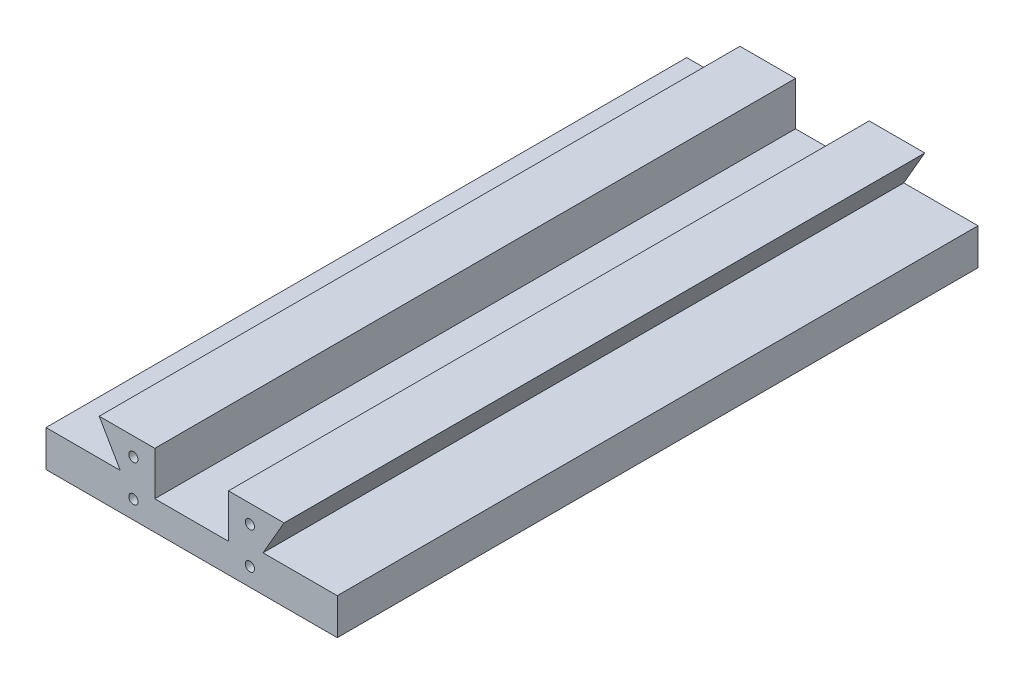
SolidWorks part; units mm, degrees
material "Ductile Iron"
ref_plane "Front Plane" through (0, 0, 0) normal (0, 0, 1) x (1, 0, 0)
ref_plane "Top Plane" through (0, 0, 0) normal (0, 1, 0) x (1, 0, 0)
ref_plane "Right Plane" through (0, 0, 0) normal (1, 0, 0) x (0, 0, -1)
sketch "dovetail-male-profile" plane through (0, 0, 0) normal (0, 0, 1) x (1, 0, 0)
  line L0 (47.4471, 31.496) -> (16.3103, 31.496)
  line L1 (-16.3103, 31.496) -> (-39.6952, 31.496)
  line L2 (16.3103, 31.496) -> (16.3103, 12.446)
  line L3 (16.3103, 12.446) -> (-16.3103, 12.446)
  line L4 (-16.3103, 12.446) -> (-16.3103, 31.496)
  line B0 (-63.5, 0) -> (63.5, 0)
  line B1 (63.5, 0) -> (63.5, 15.875)
  line B2 (63.5, 15.875) -> (38.4596, 15.875)
  line B3 (38.4596, 15.875) -> (47.625, 31.75)
  line B4 (47.625, 31.75) -> (16.0563, 31.75)
  line B5 (-40.2927, 31.75) -> (-31.1272, 15.875)
  line B6 (-31.1272, 15.875) -> (-63.5, 15.875)
  line B7 (-63.5, 15.875) -> (-63.5, 0)
  line B8 (-38.4596, 15.875) -> (-47.625, 31.75)
  line B9 (-47.625, 31.75) -> (-40.2927, 31.75)
  line B10 (-16.0563, 31.75) -> (-16.0563, 12.7)
  line B11 (-16.0563, 12.7) -> (16.0563, 12.7)
  line B12 (16.0563, 12.7) -> (16.0563, 31.75)
  line B13 (-16.0563, 31.75) -> (-40.2927, 31.75)
  line B14 (-63.5, 15.875) -> (-63.5, 47.625)
  line B15 (-63.5, 47.625) -> (63.5, 47.625)
  line B16 (63.5, 47.625) -> (63.5, 15.875)
  line B17 (-16.0563, 31.75) -> (16.0563, 31.75)
  line B18 (0, 47.625) -> (0, 0) construction
  line B19 (-38.4596, 15.875) -> (38.4596, 15.875) construction
  line B20 (-28.702, 36.957) -> (28.702, 36.957) construction
  line B21 (-25.4, 7.874) -> (25.4, 7.874) construction
  line B22 (-25.4, 7.874) -> (-25.4, 23.8125) construction
  line B23 (25.4, 7.874) -> (25.4, 23.8125) construction
  line B24 (-52.832, 23.8125) -> (52.832, 23.8125) construction
  circle B25 centre (0, 22.225) radius 18.669 construction
  line B26 (40.2927, 31.75) -> (31.1272, 15.875)
  line B27 (31.1272, 15.875) -> (38.4596, 15.875)
sketch_block_instance "dovetail pair-1"
sketch_block "dovetail pair" parameters "D8"=37.338, "D1"=60, "D2"=127, "D3"=6.35, "D4"=15.875, "D5"=31.75, "D6"=95.25, "D7"=19.05, "D9"=60, "D10"=31.75, "D11"=50.8, "D12"=23.876, "D13"=7.874, "D14"=10.668, "D15"=34.798, "D16"=21.082, "D17"=7.9375
extrude "x-guide-extrude" add sketch "dovetail-male-profile" along normal blind 279.4 contours B10 B13 B5 B6 B7 B0 B1 B2 B3 B4 B12 B11 region at (0, 11.7369, 0)
hole_wizard "end plate holes" positions "Sketch2" profile "Sketch3" tap size "#10-32" standard "ANSI Inch"
sketch "Sketch2" plane through (0, 0, 0) normal (0, 0, -1) x (-1, 0, 0)
  point P27 (-25.4, 23.8125)
  point P29 (25.4, 23.8125)
  point P31 (25.4, 7.874)
  point P33 (-25.4, 7.874)
sketch "Sketch3" plane through (25.4, 23.8125, 0) normal (1, 0, 0) x (0, 1, 0)
  line L0 (0, 0) -> (0, 13.1513)
  line L1 (0, 13.1513) -> (2.0193, 11.938)
  line L2 (2.0193, 11.938) -> (2.0193, 0)
  line L3 (2.0193, 0) -> (0, 0)
  line L4 (0, 13.1513) -> (-2.0193, 11.938) construction
  line L5 (0, -6.35) -> (0, 107.95) construction
  dimension "Tap Drill Dia." = 4.0386
  dimension "Tap Drill Depth" = 11.938
  dimension "Drill Angle" = 118
cosmetic thread "Hole Thread1" parameters "D1"=9.652, "D2"=4.826
cosmetic thread "Hole Thread2" parameters "D1"=9.652, "D2"=4.826
cosmetic thread "Hole Thread9" parameters "D1"=9.652, "D2"=4.826
cosmetic thread "Hole Thread10" parameters "D1"=9.652, "D2"=4.826
hole_wizard "end plate holes 2" positions "Sketch4" profile "Sketch5" tap size "#10-32" standard "ANSI Inch"
sketch "Sketch4" plane through (0, 0, 279.4) normal (0, 0, 1) x (1, 0, 0)
  point P8 (25.4, 23.8125)
  point P10 (25.4, 7.874)
  point P12 (-25.4, 7.874)
  point P14 (-25.4, 23.8125)
cosmetic thread "Hole Thread5" parameters "D1"=9.652, "D2"=4.826
cosmetic thread "Hole Thread6" parameters "D1"=9.652, "D2"=4.826
cosmetic thread "Hole Thread11" parameters "D1"=9.652, "D2"=4.826
cosmetic thread "Hole Thread12" parameters "D1"=9.652, "D2"=4.826
sketch "Sketch5" plane through (25.4, 23.8125, 279.4) normal (1, 0, 0) x (0, -1, 0)
  line L0 (0, 0) -> (0, 13.1513)
  line L1 (0, 13.1513) -> (2.0193, 11.938)
  line L2 (2.0193, 11.938) -> (2.0193, 0)
  line L5 (2.0193, 0) -> (0, 0)
  line L10 (0, 13.1513) -> (-2.0193, 11.938) construction
  line L11 (0, -6.35) -> (0, 107.95) construction
  dimension "Tap Drill Dia." = 4.0386
  dimension "Tap Drill Depth" = 11.938
  dimension "Drill Angle" = 118
equation "\"dovetail-angle\" = 60"
equation "\"dovetail-stock-width\" = 5"
equation "\"dovetail-stock-height\" = 1.25"
equation "\"dovetail-throat-width\" = \"dovetail-stock-width\" - (2 * \"dovetail-depth\")"
equation "\"dovetail-depth\" = 0.5 * \"dovetail-stock-height\""
equation "\"delta-x\" = 6"
equation "\"delta-y\" = 3"
equation "\"gib-thickness\" = 0.25"
equation "\"x-slide-length\" = \"dovetail-stock-width\" + \"delta-x\""
equation "\"y-slide-length\" = \"dovetail-stock-width\" + \"delta-y\""
equation "\"D1@x-guide-extrude\"=\"x-slide-length\""
equation "\"dog-point-diam\" = .149"
equation "\"dog-point-length\" = .067"
equation "\"dovetail-double-height\" = 2 * \"dovetail-depth\" + 0.5"
equation "\"acme-major-diam\" = .5"
equation "\"acme-pitch-diam\" = 0.45"
equation "\"acme-minor-diam\" = 0.4"
equation "\"acme-nut-od\" = 1.47"
equation "\"acme-nut-length\" = 1"
equation "\"acme-nut-trim-height\" = .75"
equation "\"screw-bearing-od\" = 0.5"
equation "\"screw-bearing-length\" = .375"
equation "\"end-plate-thickness\" = \"screw-bearing-length\""
equation "\"screw-bearing-id\" = .375"
equation "\"screw-add-length\" = 2 * \"end-plate-thickness\" + 1 + 0.5"
equation "\"acme-nut-mount-hole-space-horz\" = 0.95"
equation "\"acme-nut-mount-hole-space-vert\" = 0.5 * \"acme-nut-length\""
equation "\"x-screw-length\" = \"x-slide-length\" + \"screw-add-length\""
equation "\"y-screw-length\" = \"y-slide-length\" + \"screw-add-length\""
equation "\"D2@dovetail pair\"=\"dovetail-stock-width\""
equation "\"D1@dovetail pair\"=\"dovetail-angle\""
equation "\"D3@dovetail pair\"=\"gib-thickness\""
equation "\"D4@dovetail pair\"=\"dovetail-depth\""
equation "\"D5@dovetail pair\"=\"dovetail-stock-height\""
equation "\"D6@dovetail pair\"=\"dovetail-throat-width\""
equation "\"D10@dovetail pair\"=\"dovetail-stock-height\""
equation "\"D7@dovetail pair\"=\"acme-nut-trim-height\""
equation "\"D8@dovetail pair\"=\"acme-nut-od\""
equation "\"D9@dovetail pair\"=\"dovetail-angle\""
equation "\"D17@dovetail pair\"=\"dovetail-depth\"/2"
